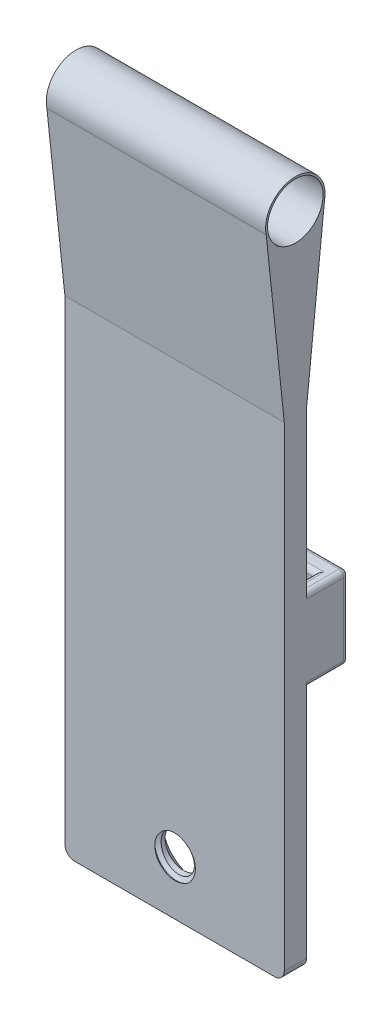
SolidWorks part; units mm, degrees
material "Black Leather"
ref_plane "Front Plane" through (0, 0, 0) normal (0, 0, 1) x (1, 0, 0)
ref_plane "Top Plane" through (0, 0, 0) normal (0, 1, 0) x (1, 0, 0)
ref_plane "Right Plane" through (0, 0, 0) normal (1, 0, 0) x (0, 0, -1)
sketch "Sketch1" plane through (0, 0, 0) normal (1, 0, 0) x (0, 0, -1)
  circle A0 centre (0, 0) radius 2.85
  circle A1 centre (0, 0) radius 3.05
  dimension "D1" = 5.7
  dimension "D2" = 6.1
extrude "Boss-Extrude1" add sketch "Sketch1" along normal blind 22.5
sketch "Sketch3" plane through (0, 0, 0) normal (1, 0, 0) x (0, 0, -1)
  line L0 (-3.05, 0) -> (3.05, 0)
  line L1 (3.05, 0) -> (1.164, -17.9442)
  line L6 (-3.05, 0) -> (-1.136, -18.2104)
  line L11 (-1.136, -67.9442) -> (1.164, -67.9442)
  line L13 (1.164, -17.9442) -> (1.164, -67.9442)
  line L14 (-1.136, -18.2104) -> (-1.136, -67.9442)
  circle A0 centre (0, 0) radius 3.05 construction
  dimension "D1" = 2.3
  dimension "D2" = 50
  dimension "D3" = 96
  dimension "D4" = 96
ref_plane "Plane1" through (0, -2.85, 0) normal (0, -1, 0) x (-1, 0, 0)
sketch "Sketch4" plane through (0, -2.85, 0) normal (0, -1, 0) x (-1, 0, 0)
  line L0 (0, 0) -> (-22.5, 0)
  dimension "D1" = 22.5
sweep "Sweep1" add profiles "Sketch3" path "Sketch4"
hole_wizard "CSK for #6 Flat Head Machine Screw (100)1" positions "Sketch5" profile "Sketch7" countersink size "#6" standard "ANSI Inch" end condition up to next
sketch "Sketch5" plane through (0, 0, -1.164) normal (0, 0, -1) x (-1, 0, 0)
  line L0 (0, -67.9442) -> (0, -17.9442) construction
  line L1 (0, -67.9442) -> (-22.5, -67.9442) construction
  point P0 (-11.25, -62.1942)
  dimension "D1" = 11.25
  dimension "D2" = 5.75
sketch "Sketch7" plane through (11.25, -62.1942, -1.164) normal (1, 0, 0) x (0, 1, 0)
  line L0 (0, 0) -> (0, 2.3)
  line L1 (0, 2.3) -> (1.8986, 2.3)
  line L2 (1.8986, 2.3) -> (1.8986, 1.38)
  line L3 (1.8986, 1.38) -> (3.5433, 0)
  line L5 (3.5433, 0) -> (0, 0)
  line L6 (-1.8987, 1.38) -> (-3.5433, 0) construction
  line L11 (0, -6.35) -> (0, 107.95) construction
  dimension "Thru Hole Dia." = 3.7973
  dimension "Thru Hole Depth" = 2.3
  dimension "Near C'Sink Dia." = 7.0866
  dimension "Near C'Sink Angle" = 100
thread "Thread1" pitch 0.7937 method cut profile "Thread Profile1" start angle 0, offset 0, length 0, pitch 0.7937, diameter 3.7973
ref_plane "Plane2" through (13.1486, -62.1942, 0.216) normal (0, -1, 0) x (1, 0, 0)
sketch "Thread Profile1" plane through (13.1486, -62.1942, 0.216) normal (0, -1, 0) x (1, 0, 0)
  line L0 (0, 0) -> (0, 0.7937) construction
  line L1 (0, 0) -> (0.4296, 0.248)
  line L2 (0.4296, 0.248) -> (0.4296, 0.3473)
  line L3 (0.4296, 0.3473) -> (0, 0.5953)
  line L4 (0.4296, 0.2977) -> (0, 0.2977) construction
  line L11 (0, 0) -> (0, 0.5953)
  point P2 (0, 0)
  dimension "Pitch" = 0.7937
  dimension "Profile_Angle" = 60
  dimension "Profile_Land" = 0.0992
  dimension "Profile_Height" = 0.4296
sketch "Sketch12" plane through (22.5, 0, 0) normal (1, 0, 0) x (0, 0, -1)
  circle A0 centre (0, 0) radius 2.85
extrude "Cut-Extrude1" cut sketch "Sketch12" against normal up to next
sketch "Sketch13" plane through (22.5, 0, 0) normal (1, 0, 0) x (0, 0, -1)
  line L0 (1.164, -67.9442) -> (1.164, -17.9442) construction
  line L1 (1.164, -42.9442) -> (5.464, -42.9442)
  line L2 (1.164, -42.9442) -> (1.164, -34.5473)
  line L3 (1.164, -34.5473) -> (5.464, -34.5473)
  line L4 (5.464, -42.9442) -> (5.464, -34.5473)
  line L5 (-1.136, -67.9442) -> (1.164, -67.9442) construction
  dimension "D1" = 4.3
  dimension "D2" = 8.3969
  dimension "D3" = 25
extrude "Boss-Extrude2" add sketch "Sketch13" against normal blind 22.5
sketch "Sketch14" plane through (0, -42.9442, 0) normal (0, -1, 0) x (1, 0, 0)
  line L0 (0, -1.164) -> (22.5, -1.164) construction
  line L1 (1.5, -1.164) -> (21, -1.164)
  line L2 (1.5, -1.164) -> (1.5, -3.464)
  line L3 (1.5, -3.464) -> (21, -3.464)
  line L4 (21, -1.164) -> (21, -3.464)
  point P4 (11.25, -1.164)
  dimension "D1" = 2.3
  dimension "D2" = 19.5
extrude "Cut-Extrude2" cut sketch "Sketch14" against normal up to next
fillet "Fillet1" radius 1 2 edges at (0, -67.9442, -0.014) (22.5, -67.9442, -0.014)
fillet "Fillet2" radius 0.5 14 edges at (11.25, -34.5473, -5.464) (0, -38.7458, -5.464) (11.25, -42.9442, -5.464) (22.5, -38.7458, -5.464) (21, -42.9442, -2.314) (11.25, -42.9442, -3.464) (1.5, -42.9442, -2.314) (0, -42.9442, -3.314) (1.5, -34.5473, -2.314) (0, -34.5473, -3.314) (21, -34.5473, -2.314) (11.25, -34.5473, -3.464) (22.5, -34.5473, -3.314) (22.5, -42.9442, -3.314)
equation "\"D1@Sketch13\" = 0.23cm + 2mm"
equation "\"CBoot_L_nominal\"= 0.0135m"
equation "\"D2@Sketch5\"=(\"CBoot_L_nominal\"/2)-0.001m"
